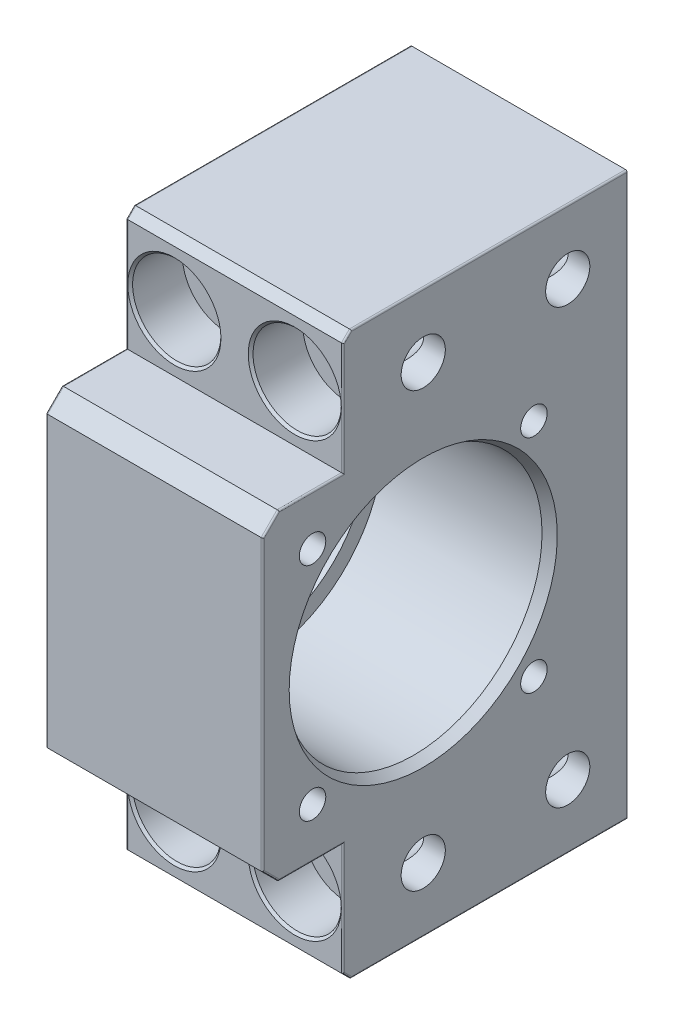
SolidWorks part; units mm, degrees
material "6063-T1"
ref_plane "Front Plane" through (0, 0, 0) normal (0, 0, 1) x (1, 0, 0)
ref_plane "Top Plane" through (0, 0, 0) normal (0, 1, 0) x (1, 0, 0)
ref_plane "Right Plane" through (0, 0, 0) normal (1, 0, 0) x (0, 0, -1)
ref_plane "Plane1" through (-13.5, 0, 0) normal (-1, 0, 0) x (0, -1, 0)
sketch "Sketch1" plane through (-13.5, 0, 0) normal (-1, 0, 0) x (0, -1, 0)
  line L0 (35, 24) -> (-35, 24)
  line L1 (-35, 24) -> (-35, -24)
  line L2 (-35, -24) -> (35, -24)
  line L3 (35, -24) -> (35, 24)
  line L4 (0, -1000) -> (0, 49000) construction
  line L5 (-1000, 0) -> (49000, 0) construction
  dimension "D1" = 48
  dimension "D2" = 70
extrude "Boss-Extrude1" add sketch "Sketch1" against normal blind 27
sketch "Sketch2" plane through (13.5, 0, 0) normal (1, 0, 0) x (0, 0, -1)
  line L0 (-24, 35) -> (-24, 20)
  line L1 (-24, 20) -> (-14, 20)
  line L2 (-14, 20) -> (-14, 35)
  line L3 (-14, 35) -> (-24, 35)
  line L5 (-24, -35) -> (-14, -35)
  line L6 (-24, -35) -> (-24, -20)
  line L7 (-24, -20) -> (-14, -20)
  line L8 (-14, -35) -> (-14, -20)
  dimension "D1" = 10
  dimension "D2" = 15
extrude "Cut-Extrude1" cut sketch "Sketch2" against normal through all
hole_wizard "Hole1" positions "Sketch5" profile "Sketch4" legacy end condition through all
sketch "Sketch5" plane through (13.5, 0, 0) normal (1, 0, 0) x (0, 0, -1)
  line L1 (24, 35) -> (24, -35) construction
  line L2 (-1000, 0) -> (49000, 0) construction
  point P0 (-4, 0)
  dimension "D1" = 28
sketch "Sketch4" plane through (13.5, 0, 4) normal (0, 1, 0) x (0, 0, -1)
  line L0 (0, 0) -> (0, 27)
  line L1 (0, 27) -> (14, 27)
  line L2 (14, 27) -> (14, 21)
  line L3 (14, 21) -> (16, 21)
  line L4 (16, 21) -> (16, 0)
  line L5 (16, 0) -> (0, 0)
  line L6 (0, 110) -> (0, -10) construction
  dimension "Diameter" = 28
  dimension "Depth" = 27
  dimension "C-Bore Diameter" = 32
  dimension "C-Bore Depth" = 21
hole_wizard "Ø5.5 (5.5) Diameter Hole1" positions "Sketch7" profile "Sketch6" hole size "Ø5.5" standard "ANSI Metric" end condition through all
sketch "Sketch7" plane through (-13.5, 0, 0) normal (-1, 0, 0) x (0, 0, 1)
  line L0 (-1000, 0) -> (49000, 0) construction
  line L1 (0, -1000) -> (0, 49000) construction
  line L2 (-24, 35) -> (-24, -35) construction
  line L3 (14, 35) -> (-24, 35) construction
  line L4 (-24, -35) -> (14, -35) construction
  point P0 (4, 27)
  point P1 (-14, 27)
  point P16 (4, -27)
  point P18 (-14, -27)
  dimension "D1" = 18
  dimension "D2" = 10
  dimension "D3" = 8
  dimension "D4" = 10
  dimension "D5" = 8
  dimension "D6" = 54
sketch "Sketch6" plane through (-13.5, 27, 4) normal (0, 1, 0) x (0, 0, 1)
  line L0 (0, 0) -> (0, 27)
  line L1 (0, 27) -> (2.75, 27)
  line L2 (2.75, 27) -> (2.75, 0)
  line L5 (2.75, 0) -> (0, 0)
  line L11 (0, -6.35) -> (0, 107.95) construction
  dimension "Thru Hole Dia." = 5.5
  dimension "Thru Hole Depth" = 27
hole_wizard "CBORE for M6 Hex Socket Thin Head Cap Screw1" positions "Sketch9" profile "Sketch8" counterbore size "M6" standard "DIN" end condition through all
sketch "Sketch9" plane through (0, 0, 14) normal (0, 0, 1) x (1, 0, 0)
  line L0 (-1000, 0) -> (49000, 0) construction
  line L1 (0, -1000) -> (0, 49000) construction
  point P0 (-7.5, -27)
  point P1 (7.5, -27)
  point P2 (7.5, 27)
  point P3 (-7.5, 27)
  dimension "D1" = 54
  dimension "D2" = 15
sketch "Sketch8" plane through (-7.5, -27, 14) normal (1, 0, 0) x (0, -1, 0)
  line L0 (0, 0) -> (0, 38)
  line L1 (3.3, 37.7) -> (3.6, 38)
  line L2 (5.5, 6.5) -> (3.3, 6.5)
  line L3 (3.3, 6.5) -> (3.3, 37.7)
  line L5 (5.5, 6.5) -> (5.5, 0.3)
  line L6 (5.5, 0.3) -> (5.8, 0)
  line L7 (5.8, 0) -> (0, 0)
  line L8 (-5.5, 0.3) -> (-5.8, 0) construction
  line L11 (0, -6.35) -> (0, 107.95) construction
  line L12 (3.6, 38) -> (0, 38)
  line L13 (-3.3, 37.7) -> (-3.6, 38) construction
  dimension "Thru Hole Dia." = 6.6
  dimension "Thru Hole Depth" = 38
  dimension "C'Bore Dia." = 11
  dimension "C'Bore Depth" = 6.5
  dimension "Near C'Sink Dia." = 11.6
  dimension "Near C'Sink Angle" = 90
  dimension "Far C'Sink Dia." = 7.2
  dimension "Far C'Sink Angle" = 90
hole_wizard "Tap Drill for M4x0.7 Tap1" positions "Sketch16" profile "Sketch15" hole size "M4x0.7" standard "ANSI Metric"
sketch "Sketch16" plane through (13.5, 0, 0) normal (-1, 0, 0) x (0, 0, 1)
  line L0 (4, 0) -> (-35351.3391, 35355.3391) construction
  line L1 (-18.3773, -22.3773) -> (35336.9617, 35332.9617) construction
  line L2 (4, -1000) -> (4, 49000) construction
  circle A0 centre (4, 0) radius 19.5 construction
  point P5 (-9.7886, 13.7886)
  point P6 (17.7886, 13.7886)
  point P7 (17.7886, -13.7886)
  point P15 (-9.7886, -13.7886)
  dimension "D1" = 39
  dimension "D2" = 90
  dimension "D3" = 45
sketch "Sketch15" plane through (13.5, 13.7886, -9.7886) normal (0, 1, 0) x (0, 0, -1)
  line L0 (0, 0) -> (0, 12.8589)
  line L1 (0, 12.8589) -> (1.65, 12)
  line L2 (1.65, 12) -> (1.65, 0)
  line L5 (1.65, 0) -> (0, 0)
  line L10 (0, 12.8589) -> (-1.65, 12) construction
  line L11 (0, -6.35) -> (0, 107.95) construction
  dimension "Hole Dia." = 3.3
  dimension "Hole Depth" = 12
  dimension "Drill Angle" = 125
cosmetic thread "Cosmetic Thread1" parameters "D2"=4
cosmetic thread "Cosmetic Thread2" parameters "D2"=4
cosmetic thread "Cosmetic Thread3" parameters "D2"=4
cosmetic thread "Cosmetic Thread4" parameters "D2"=4
chamfer "Chamfer1" distance 1 angle 45 4 edges at (0, -35, -24) (0, 35, -24) (0, 35, 14) (0, -35, 14)
chamfer "Chamfer3" distance 2 angle 45 2 edges at (0, 20, 24) (0, -20, 24)
chamfer "Chamfer2" distance 0.7 distance2 1.2 1 edges at (13.5, 0, -12) first distance on face at (13.5, 13.7886, -11.4386)
chamfer "Chamfer4" distance 0.5 angle 45 1 edges at (-13.5, 0, -10)
fillet "Fillet1" radius 0.2 28 edges at (13.5, 35, -5) (13.5, 34.5, 13.5) (13.5, 27, 14) (13.5, 20, 18) (-13.5, 34.5, -23.5) (-13.5, 0, -24) (-13.5, -34.5, -23.5) (-13.5, -35, -5) (-13.5, -34.5, 13.5) (-13.5, 35, -5) (-13.5, 34.5, 13.5) (-13.5, 19, 23) (-13.5, 20, 18) (-13.5, 27, 14) (-13.5, -27, 14) (-13.5, -20, 18) (-13.5, -19, 23) (-13.5, 0, 24) (13.5, 19, 23) (13.5, 0, 24) (13.5, -19, 23) (13.5, -20, 18) (13.5, -27, 14) (13.5, -34.5, 13.5) (13.5, -35, -5) (13.5, -34.5, -23.5) (13.5, 0, -24) (13.5, 34.5, -23.5)
sketch "Sketch18" plane through (-13.5, 0, 0) normal (-1, 0, 0) x (0, 0, 1)
  line L1 (-23, 35) -> (13, 35) construction
  line L3 (-21.4, 35) -> (-21.4, -35)
  line L6 (13, -35) -> (-23, -35) construction
  line L7 (-21.4, -35) -> (-24, -35)
  line L8 (-24, -35) -> (-24, 35)
  line L9 (-24, 35) -> (-21.4, 35)
  line L10 (-24, -34) -> (-24, 34) construction
  circle A0 centre (4, 0) radius 14 construction
  point P14 (-21.4, 0)
  dimension "D2" = 25.4
extrude "Cut-Extrude2" cut sketch "Sketch18" against normal through all
